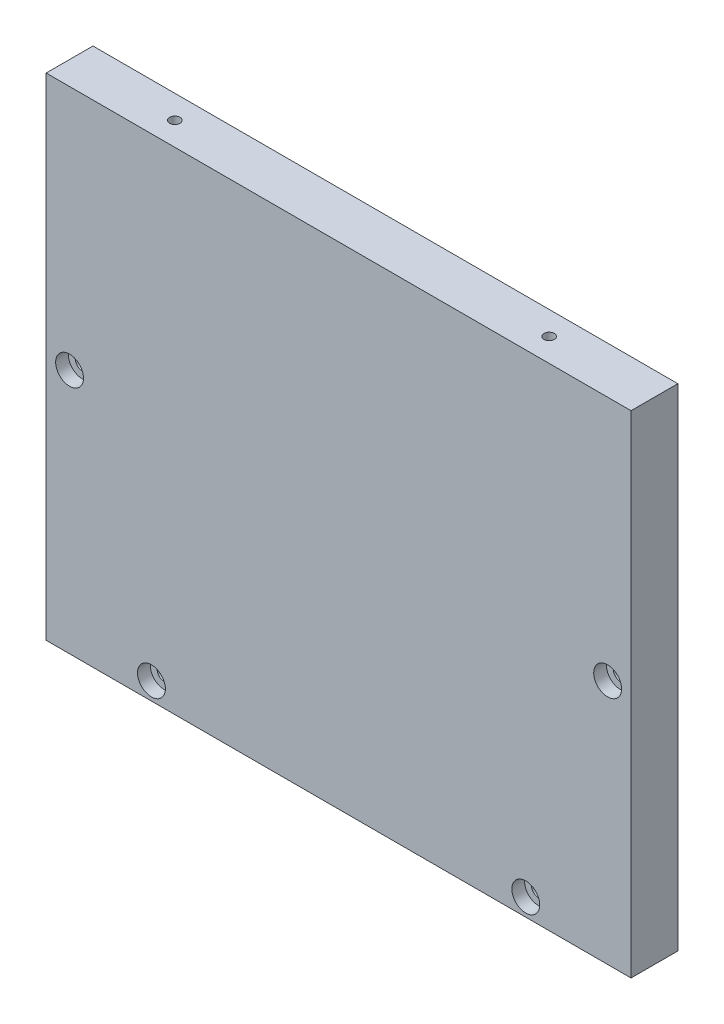
SolidWorks part; units mm, degrees
ref_plane "Front Plane" through (0, 0, 0) normal (0, 0, 1) x (1, 0, 0)
ref_plane "Top Plane" through (0, 0, 0) normal (0, 1, 0) x (1, 0, 0)
ref_plane "Right Plane" through (0, 0, 0) normal (1, 0, 0) x (0, 0, -1)
sketch "Sketch1" plane through (0, 0, 0) normal (0, 0, 1) x (1, 0, 0)
  line L1 (-50, 42) -> (50, 42)
  line L2 (-50, 42) -> (-50, -42)
  line L3 (-50, -42) -> (50, -42)
  line L4 (50, 42) -> (50, -42)
  line L5 (-50, 42) -> (50, -42) construction
  line L6 (-50, -42) -> (50, 42) construction
  point P0 (0, 0)
extrude "Boss-Extrude1" add sketch "Sketch1" along normal blind 8
sketch "Sketch2" plane through (0, 0, 8) normal (0, 0, 1) x (1, 0, 0)
  line L0 (-50, -42) -> (-50, -36) construction
  line L1 (-50, -36) -> (50, -36) construction
  line L2 (50, -42) -> (50, 42) construction
  line L3 (50, -36) -> (50, -42) construction
  line L4 (-50, -39) -> (-32, -39) construction
  line L5 (50, -39) -> (32, -39) construction
  point P12 (0, 0)
  point P13 (0, 0)
hole_wizard "CBORE for #2 Socket Head Cap Screw1" positions "3DSketch1" profile "Sketch3" counterbore size "#2" standard "ANSI Inch"
sketch3d "3DSketch1"
  point P0 (-32, -39, 8)
  point P3 (32, -39, 8)
sketch "Sketch3" plane through (-32, -39, 8) normal (1, 0, 0) x (0, -1, 0)
  line L0 (0, 0) -> (0, 13.0026)
  line L1 (0, 13.0026) -> (1.2192, 12.27)
  line L2 (1.2192, 12.27) -> (1.2192, 2.1844)
  line L3 (1.2192, 2.1844) -> (2.3812, 2.1844)
  line L4 (2.3812, 2.1844) -> (2.3812, 0)
  line L5 (2.3812, 0) -> (0, 0)
  line L10 (0, 13.0026) -> (-1.2192, 12.27) construction
  line L11 (0, -6.35) -> (0, 107.95) construction
  dimension "Hole Dia." = 2.4384
  dimension "Hole Depth" = 12.27
  dimension "C'Bore Dia." = 4.7625
  dimension "C'Bore Depth" = 2.1844
  dimension "Drill Angle" = 118
sketch "Sketch4" plane through (0, 0, 8) normal (0, 0, 1) x (1, 0, 0)
  line L0 (-50, -42) -> (-42, -42) construction
  line L1 (-42, -42) -> (-42, 42) construction
  line L2 (50, 42) -> (-50, 42) construction
  line L3 (-42, 42) -> (-50, 42) construction
  line L4 (50, -42) -> (42, -42) construction
  line L5 (42, -42) -> (42, 42) construction
  line L6 (42, 42) -> (50, 42) construction
  line L7 (46, -42) -> (46, 0) construction
  line L8 (-46, -42) -> (-46, 0) construction
hole_wizard "CBORE for #2 Socket Head Cap Screw2" positions "3DSketch2" profile "Sketch5" counterbore size "#2" standard "ANSI Inch"
sketch3d "3DSketch2"
  point P0 (-46, 0, 8)
  point P3 (46, 0, 8)
sketch "Sketch5" plane through (-46, 0, 8) normal (1, 0, 0) x (0, -1, 0)
  line L0 (0, 0) -> (0, 13.0026)
  line L1 (0, 13.0026) -> (1.2192, 12.27)
  line L2 (1.2192, 12.27) -> (1.2192, 2.1844)
  line L3 (1.2192, 2.1844) -> (2.3812, 2.1844)
  line L4 (2.3812, 2.1844) -> (2.3812, 0)
  line L5 (2.3812, 0) -> (0, 0)
  line L10 (0, 13.0026) -> (-1.2192, 12.27) construction
  line L11 (0, -6.35) -> (0, 107.95) construction
  dimension "Hole Dia." = 2.4384
  dimension "Hole Depth" = 12.27
  dimension "C'Bore Dia." = 4.7625
  dimension "C'Bore Depth" = 2.1844
  dimension "Drill Angle" = 118
sketch "Sketch6" plane through (0, 42, 0) normal (0, 1, 0) x (1, 0, 0)
  line L0 (-50, -4) -> (-32, -4) construction
  line L1 (-50, -8) -> (-50, 0) construction
  line L2 (50, -4) -> (32, -4) construction
  line L3 (50, -8) -> (50, 0) construction
hole_wizard "#2-56 Tapped Hole1" positions "3DSketch3" profile "Sketch7" tap size "#2-56" standard "ANSI Inch"
sketch3d "3DSketch3"
  point P0 (-32, 42, 4)
  point P3 (32, 42, 4)
sketch "Sketch7" plane through (-32, 42, 4) normal (1, 0, 0) x (0, 0, 1)
  line L0 (0, 0) -> (0, 12.5342)
  line L1 (0, 12.5342) -> (0.889, 12)
  line L2 (0.889, 12) -> (0.889, 0)
  line L5 (0.889, 0) -> (0, 0)
  line L10 (0, 12.5342) -> (-0.889, 12) construction
  line L11 (0, -6.35) -> (0, 107.95) construction
  dimension "Tap Drill Dia." = 1.778
  dimension "Tap Drill Depth" = 12
  dimension "Drill Angle" = 118
cosmetic thread "Hole Thread1" parameters "D1"=10, "D2"=2.1844
cosmetic thread "Hole Thread2" parameters "D1"=10, "D2"=2.1844
